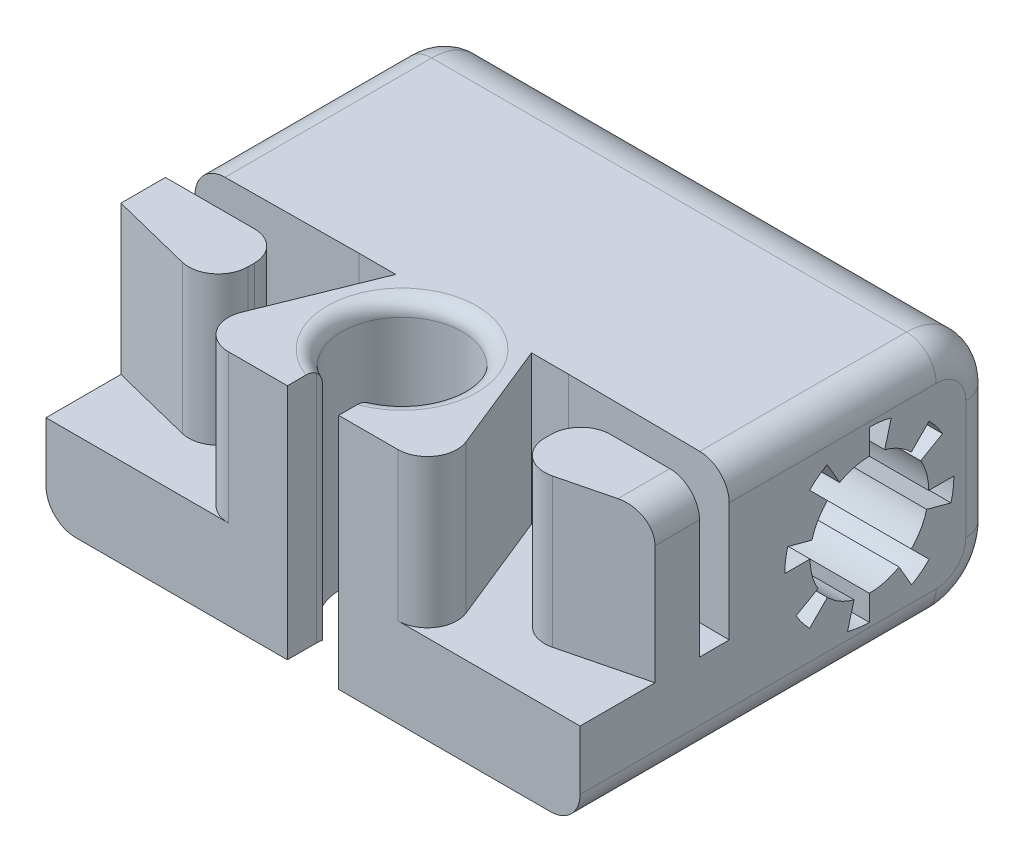
SolidWorks part; units mm, degrees
ref_plane "Alzado" through (0, 0, 0) normal (0, 0, 1) x (1, 0, 0)
ref_plane "Planta" through (0, 0, 0) normal (0, 1, 0) x (1, 0, 0)
ref_plane "Vista lateral" through (0, 0, 0) normal (1, 0, 0) x (0, 0, -1)
sketch "Croquis1" plane through (0, 0, 0) normal (0, 1, 0) x (1, 0, 0)
  line L0 (-16.125, -12.8625) -> (37.0847, -12.8625) construction
  line L1 (-16.125, 9.1375) -> (19.875, 9.1375)
  line L2 (-16.125, 9.1375) -> (-16.125, -18.8625)
  line L3 (-16.125, -18.8625) -> (0.1467, -18.8625)
  line L4 (19.875, 9.1375) -> (19.875, -18.8625)
  line L5 (19.875, 9.1375) -> (-16.125, -18.8625) construction
  line L6 (1.875, -16.9125) -> (1.875, -18.8125) construction
  line L7 (3.6033, -16.9125) -> (3.6033, -18.8625)
  line L8 (0.1467, -16.9125) -> (0.1467, -18.8625)
  line L9 (3.6033, -18.8625) -> (19.875, -18.8625)
  line L10 (-16.1265, 0.6375) -> (22.0746, 0.6375) construction
  line L11 (1.875, -12.8625) -> (1.875, 9.1375) construction
  arc A0 (3.5635, -16.5437) -> (0.1865, -16.5437) centre (1.875, -12.8625) ccw
  arc A1 (3.6033, -16.9125) -> (3.5635, -16.5437) centre (1.875, -16.9125) ccw
  arc A3 (0.1865, -16.5437) -> (0.1467, -16.9125) centre (1.875, -16.9125) ccw
  point P10 (1.875, -17.8625)
  dimension "D4" = 3.4566
  dimension "D7" = 4.05
  dimension "D1" = 18
  dimension "D2" = 28
  dimension "D3" = 6
  dimension "D5" = 13.5
  dimension "D6" = 18
extrude "Saliente-Extruir1" add sketch "Croquis1" along normal blind 16
sketch "Croquis5" plane through (19.875, 0, 0) normal (1, 0, 0) x (0, 0, -1)
  line L0 (-12.8625, 19.8022) -> (-12.8625, -6.4895) construction
  line L1 (-18.8625, 16) -> (-18.8625, 0) construction
  line L2 (0.6375, 20.6011) -> (0.6375, -8.3415) construction
  line L3 (-18.8625, 8) -> (9.5862, 8) construction
  circle A0 centre (0.6375, 8) radius 5.7
  dimension "D3" = 11.4
  dimension "D1" = 6
  dimension "D2" = 13.5
extrude "Cortar-Extruir1" cut sketch "Croquis5" against normal blind 38
sketch "Croquis8" plane through (0, 0, 0) normal (0, -1, 0) x (1, 0, 0)
  line L2 (-2.175, 12.8625) -> (5.925, 12.8625)
  arc A0 (0.1865, 16.5437) -> (3.5635, 16.5437) centre (1.875, 12.8625) ccw construction
  arc A1 (-2.175, 12.8625) -> (5.925, 12.8625) centre (1.875, 12.8625) ccw
extrude "Saliente-Extruir2" add sketch "Croquis8" against normal blind 0.3
sketch "Croquis9" plane through (0, 16, 0) normal (0, 1, 0) x (1, 0, 0)
  line L0 (1.875, -12.8625) -> (1.875, 4.8397) construction
  line L1 (5.925, -12.8625) -> (-2.175, -12.8625) construction
  line L2 (-2.175, -12.8625) -> (-2.175, 5.5668) construction
  line L4 (-8.125, -10.8125) -> (-8.125, -15.8125)
  line L5 (-8.125, -15.8125) -> (-16.125, -13.8125)
  line L6 (-16.125, -13.8125) -> (-16.125, -18.8625)
  line L21 (1.875, -8.8125) -> (-16.125, -8.8125) construction
  line L25 (-2.7007, -8.7125) -> (-6.8016, -18.8625)
  line L26 (-5.1792, -8.7125) -> (-2.7007, -8.7125)
  line L27 (-5.1792, -8.7125) -> (-16.125, -8.8125)
  line L28 (-16.125, 9.1375) -> (-16.125, -18.8625) construction
  line L29 (-16.125, -8.8125) -> (-16.125, -10.8125)
  line L30 (-8.125, -10.8125) -> (-16.125, -10.8125)
  line L31 (-16.125, -18.8625) -> (-6.8016, -18.8625)
  arc A0 (3.5635, -16.5437) -> (0.1865, -16.5437) centre (1.875, -12.8625) ccw construction
  arc A1 (5.925, -12.8625) -> (-2.175, -12.8625) centre (1.875, -12.8625) ccw construction
  dimension "D1" = 2
  dimension "D2" = 3
  dimension "D3" = 5
  dimension "D4" = 8
extrude "Cortar-Extruir2" cut sketch "Croquis9" against normal blind 10
fillet "Redondeo1" radius 4 2 edges at (1.875, 16, -9.1375) (1.875, 0, -9.1375)
fillet "Redondeo2" radius 2 10 edges at (-16.125, 16, 1.8375) (-16.125, 14.8284, -7.9659) (-16.125, 8, -9.1375) (-16.125, 1.1716, -7.9659) (19.875, 0, 6.8625) (19.875, 16, 6.8625) (-16.125, 0, 6.8625) (19.875, 1.1716, -7.9659) (19.875, 8, -9.1375) (19.875, 14.8284, -7.9659)
fillet "Redondeo3" radius 1 1 edges at (1.875, 16, 8.8125)
sketch "Croquis10" plane through (-16.125, 0, 0) normal (-1, 0, 0) x (0, 0, 1)
  line L0 (-0.6375, 4) -> (-0.6375, 2.3)
  line L1 (-2.6375, 4.5359) -> (-3.4875, 3.0637)
  circle A0 centre (-0.6375, 8) radius 5.7 construction
  arc A1 (-3.4875, 3.0637) -> (-0.6375, 2.3) centre (-0.6375, 8) ccw
  arc A2 (-2.6375, 4.5359) -> (-0.6375, 4) centre (-0.6375, 8) ccw
  dimension "D1" = 30
fillet "Filete1" radius 2 2 edges at (-8.125, 11, 15.8125) (-8.125, 11, 10.8125)
extrude "Saliente-Extruir3" add sketch "Croquis10" against normal blind 36
ref_axis "Eixo1" through (-16.125, 8, -0.6375) along (1, 0, 0)
pattern_circular "PadrãoCircular1" count 8 over 360 about axis through (-16.125, 8, -0.6375) along (1, 0, 0) of "Saliente-Extruir3"
fillet "Filete2" radius 2 1 edges at (-6.8016, 11, 18.8625)
ref_plane "Plano1" through (1.875, 0, 0) normal (-1, 0, 0) x (0, 0, 1)
mirror "Espelhar3" about plane through (1.875, 0, 0) normal (-1, 0, 0) of "Cortar-Extruir2"
fillet "Filete3" radius 2 3 edges at (10.5516, 11, 18.8625) (11.875, 11, 15.8125) (11.875, 11, 10.8125)
